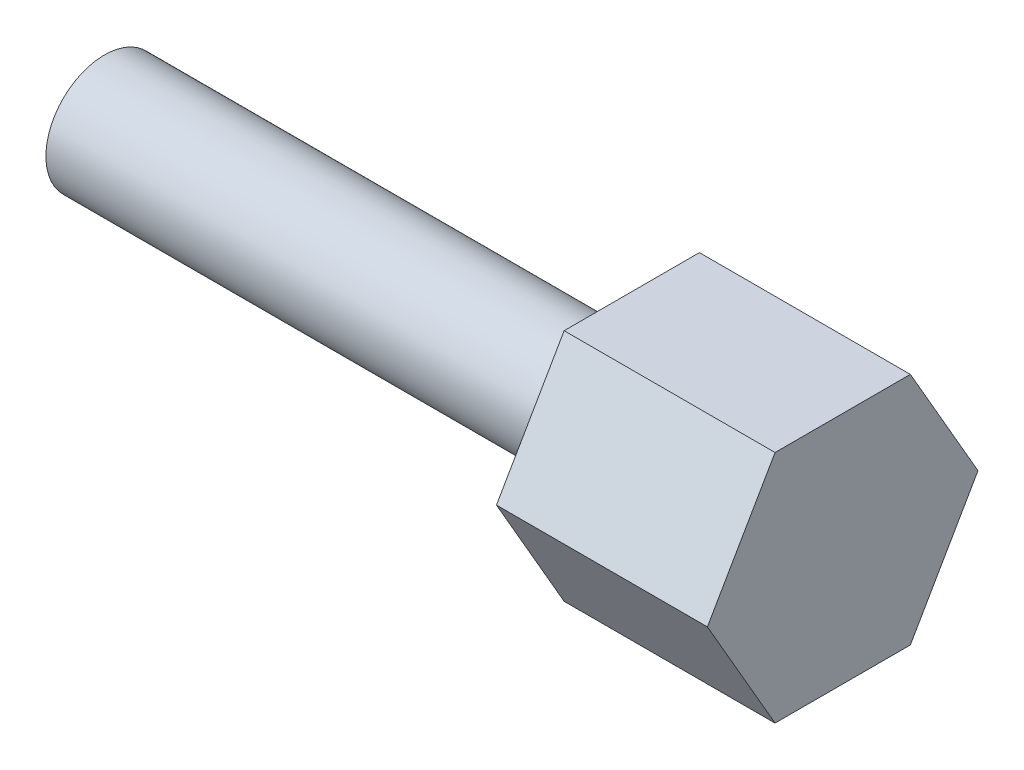
SolidWorks part; units mm, degrees
ref_plane "Front Plane" through (0, 0, 0) normal (0, 0, 1) x (1, 0, 0)
ref_plane "Top Plane" through (0, 0, 0) normal (0, 1, 0) x (1, 0, 0)
ref_plane "Right Plane" through (0, 0, 0) normal (1, 0, 0) x (0, 0, -1)
sketch "Sketch1" plane through (0, 0, 0) normal (1, 0, 0) x (0, 0, -1)
  line L1 (3.6662, 6.35) -> (-3.6662, 6.35)
  line L2 (-3.6662, 6.35) -> (-7.3323, 0)
  line L3 (-7.3323, 0) -> (-3.6662, -6.35)
  line L4 (-3.6662, -6.35) -> (3.6662, -6.35)
  line L5 (3.6662, -6.35) -> (7.3323, 0)
  line L6 (7.3323, 0) -> (3.6662, 6.35)
  circle A0 centre (0, 0) radius 3.175
  circle A1 centre (0, 0) radius 6.35 construction
  dimension "D1" = 12.7
  dimension "D2" = 6.35
extrude "Boss-Extrude1" add sketch "Sketch1" along normal blind 11.43 contours A0 | L5 L6 L1 L2 L3 L4 A0 region at (0, 3.078, -5.3313) region at (0, 0, 0)
extrude "Boss-Extrude2" add sketch "Sketch1<3>" against normal blind 28.575 contours A0 region at (0, 0, 0)
sketch "Sketch1<3>" plane through (0, 0, 0) normal (1, 0, 0) x (0, 0, -1) same geometry as "Sketch1"
